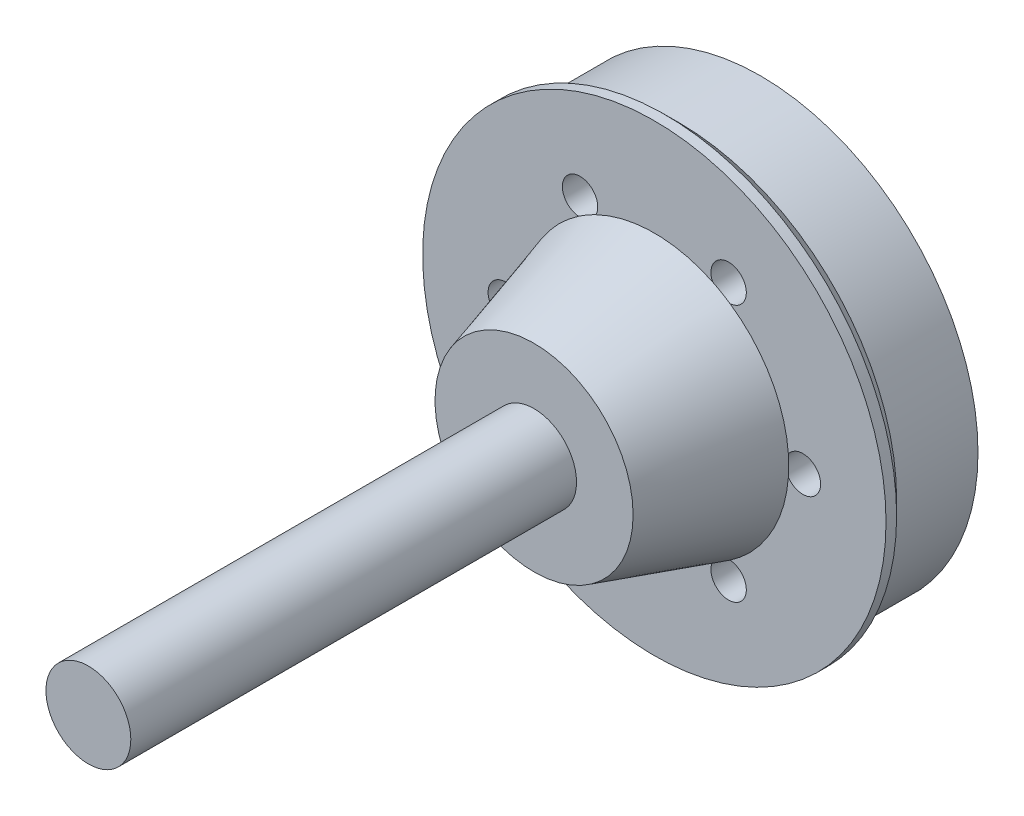
SolidWorks part; units mm, degrees
ref_plane "Front Plane" through (0, 0, 0) normal (0, 0, 1) x (1, 0, 0)
ref_plane "Top Plane" through (0, 0, 0) normal (0, 1, 0) x (1, 0, 0)
ref_plane "Right Plane" through (0, 0, 0) normal (1, 0, 0) x (0, 0, -1)
sketch "Sketch1" plane through (0, 0, 0) normal (0, 0, 1) x (1, 0, 0)
  circle A0 centre (0, 0) radius 32.75
  dimension "D1" = 65.5
extrude "Boss-Extrude1" add sketch "Sketch1" against normal mid plane 161.5
sketch "Sketch10" plane through (0, 0, 0) normal (1, 0, 0) x (0, 0, -1)
  line L0 (-97.75, 0) -> (-97.75, 14)
  line L1 (-80.75, 19) -> (-97.75, 14)
  line L2 (-1000, 0) -> (49000, 0) construction
  line L3 (-97.75, 0) -> (-80.75, 0)
  line L4 (-80.75, 0) -> (-80.75, 19)
  line L6 (-80.75, 32.75) -> (-80.75, -32.75) construction
  point P3 (-97.75, 0)
  dimension "D1" = 14
  dimension "D2" = 17
  dimension "D3" = 19
revolve "Revolve1" add sketch "Sketch10" angle 360 about L2
sketch "Sketch12" plane through (0, 0, 97.75) normal (0, 0, 1) x (1, 0, 0)
  circle A0 centre (0, 0) radius 6
  dimension "D1" = 12
extrude "Boss-Extrude5" add sketch "Sketch12" along normal blind 63
sketch "Sketch13" plane through (0, 0, 80.75) normal (0, 0, 1) x (1, 0, 0)
  circle A0 centre (21, 0) radius 2.5
  dimension "D2" = 5
  dimension "D1" = 21
extrude "Cut-Extrude1" cut sketch "Sketch13" against normal blind 10
pattern_circular "CirPattern1" count 6 over 360 about axis through (0, 0, 97.75) along (0, 0, 1) of "Cut-Extrude1"
sketch "Sketch14" plane through (0, 0, -80.75) normal (0, 0, -1) x (-1, 0, 0)
  circle A0 centre (21, 0) radius 3
  dimension "D2" = 6
  dimension "D1" = 21
extrude "Cut-Extrude2" cut sketch "Sketch14" against normal blind 10
pattern_circular "CirPattern2" count 4 over 360 about axis through (0, 0, -80.75) along (0, 0, 1) of "Cut-Extrude2"
sketch "Sketch15" plane through (0, 0, 80.75) normal (0, 0, 1) x (1, 0, 0)
  circle A0 centre (0, 0) radius 69.1607
extrude "Cut-Extrude3" cut sketch "Sketch15" against normal through all from offset 15 offset against normal yes
shell "Shell1" [suppressed] thickness 2
sketch "Sketch16" plane through (0, 0, 65.75) normal (0, 0, -1) x (-1, 0, 0)
  circle A0 centre (0, 0) radius 30.75
  circle A1 centre (0, 0) radius 32.75 construction
  circle A2 centre (0, 0) radius 54.8885
  dimension "D1" = 2
extrude "Cut-Extrude4" cut sketch "Sketch16" against normal offset from surface (13.5 mm away) 1.5 up to face at (0, 0, 80.75)
chamfer "Chamfer1" distance 2 angle 45 1 edges at (30.75, 0, 79.25)
